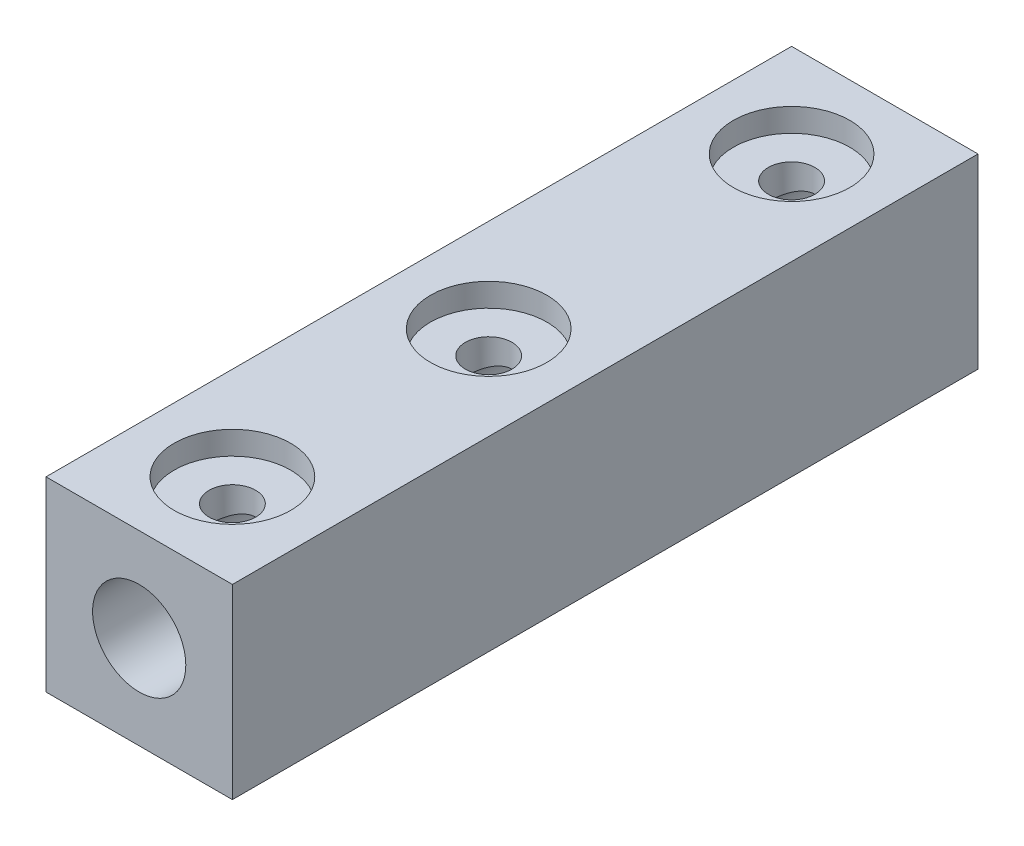
SolidWorks part; units mm, degrees
material "AISI 304"
ref_plane "Front Plane" through (0, 0, 0) normal (0, 0, 1) x (1, 0, 0)
ref_plane "Top Plane" through (0, 0, 0) normal (0, 1, 0) x (1, 0, 0)
ref_plane "Right Plane" through (0, 0, 0) normal (1, 0, 0) x (0, 0, -1)
sketch "Sketch18" plane through (0, 0, 0) normal (0, 0, 1) x (1, 0, 0)
  line L1 (12.7, 12.7) -> (-12.7, 12.7)
  line L2 (12.7, 12.7) -> (12.7, -12.7)
  line L3 (12.7, -12.7) -> (-12.7, -12.7)
  line L4 (-12.7, 12.7) -> (-12.7, -12.7)
  line L5 (12.7, 12.7) -> (-12.7, -12.7) construction
  line L6 (12.7, -12.7) -> (-12.7, 12.7) construction
  point P0 (0, 0)
  dimension "D1" = 25.4
  dimension "D2" = 25.4
extrude "Boss-Extrude3" add sketch "Sketch18" along normal mid plane 101.6
hole_wizard "1/2 (0.5) Diameter Hole2" positions "Sketch24" profile "Sketch25" hole size "1/2" standard "ANSI Inch" end condition through all
sketch "Sketch24" plane through (0, 0, 50.8) normal (0, 0, 1) x (1, 0, 0)
  point P0 (0, 0)
sketch "Sketch25" plane through (0, 0, 50.8) normal (1, 0, 0) x (0, -1, 0)
  line L0 (0, 0) -> (0, 101.6)
  line L1 (0, 101.6) -> (6.35, 101.6)
  line L2 (6.35, 101.6) -> (6.35, 0)
  line L5 (6.35, 0) -> (0, 0)
  line L11 (0, -6.35) -> (0, 107.95) construction
  dimension "Thru Hole Dia." = 12.7
  dimension "Thru Hole Depth" = 101.6
sketch "Sketch26" plane through (0, 12.7, 0) normal (0, 1, 0) x (1, 0, 0)
  line L1 (0, -3.175) -> (0, 88.9) construction
  line L3 (0, -38.1) -> (0, -50.8) construction
  line L4 (12.7, -50.8) -> (-12.7, -50.8) construction
  circle A0 centre (0, -38.1) radius 3.175
  circle A1 centre (0, -3.175) radius 3.175
  circle A2 centre (0, 38.1) radius 3.175
  circle A3 centre (0, 88.9) radius 3.175 construction
  dimension "D1" = 6.35
  dimension "D2" = 12.7
  dimension "D3" = 92.075
  dimension "D4" = 34.925
  dimension "D5" = 50.8
extrude "Cut-Extrude10" cut sketch "Sketch26" against normal blind 12.7
sketch "Sketch27" plane through (0, 12.7, 0) normal (0, 1, 0) x (1, 0, 0)
  circle A1 centre (0, 38.1) radius 7.9375
  circle A2 centre (0, -3.175) radius 7.9375
  circle A3 centre (0, -38.1) radius 7.9375
  dimension "D1" = 15.875
extrude "Cut-Extrude11" cut sketch "Sketch27" against normal blind 3.175
sketch "Sketch28" plane through (0, -12.7, 0) normal (0, -1, 0) x (1, 0, 0)
  circle A0 centre (0, 3.175) radius 3.175
  circle A1 centre (0, 3.175) radius 3.175 construction
  dimension "D1" = 6.35
extrude "Cut-Extrude12" cut sketch "Sketch28" against normal blind 12.7
sketch "Sketch29" plane through (0, -12.7, 0) normal (0, -1, 0) x (-1, 0, 0)
  circle A0 centre (0, -3.175) radius 7.9375
  circle A1 centre (0, -3.175) radius 3.175 construction
  dimension "D1" = 15.875
extrude "Cut-Extrude13" cut sketch "Sketch29" against normal blind 3.175
